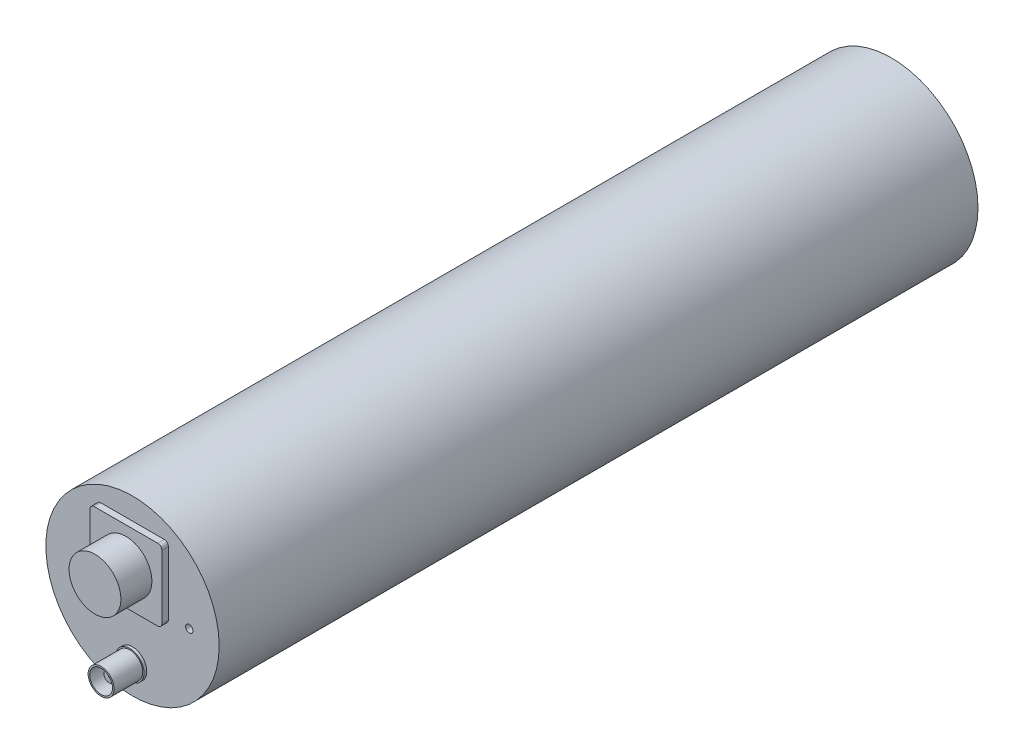
SolidWorks part; units mm, degrees
ref_plane "Front Plane" through (0, 0, 0) normal (0, 0, 1) x (1, 0, 0)
ref_plane "Top Plane" through (0, 0, 0) normal (0, 1, 0) x (1, 0, 0)
ref_plane "Right Plane" through (0, 0, 0) normal (1, 0, 0) x (0, 0, -1)
ref_axis "Axis1" through (0, 0, -88.99) along (0, 0, 1)
ref_axis "Axis2" through (0, -55, 0) along (0, 1, 0)
ref_axis "Axis3" through (-88.99, 0, 0) along (1, 0, 0)
sketch "Sketch1" plane through (0, 0, 0) normal (0, 0, 1) x (1, 0, 0)
  circle A0 centre (0, 0) radius 31.75
  dimension "D1" = 63.5
extrude "Boss-Extrude1" add sketch "Sketch1" along normal mid plane 278
sketch "Sketch3" plane through (0, 0, 139) normal (0, 0, 1) x (1, 0, 0)
  line L0 (-20.7962, 0) -> (20.7962, 0) construction
  line L1 (11.6445, -2.539) -> (-11.6445, -2.539)
  line L2 (13.1445, -1.039) -> (13.1445, 22.25)
  line L3 (11.6445, 23.75) -> (-11.6445, 23.75)
  line L4 (-13.1445, -1.039) -> (-13.1445, 22.25)
  line L5 (13.1445, -2.539) -> (-13.1445, 23.75) construction
  line L6 (13.1445, 23.75) -> (-13.1445, -2.539) construction
  line L7 (0, 0) -> (0, -21.35) construction
  arc A0 (13.1445, 22.25) -> (11.6445, 23.75) centre (11.6445, 22.25) ccw
  circle A2 centre (0, 0) radius 31.75 construction
  circle A3 centre (0, 10.6055) radius 9.5
  arc A4 (11.6445, -2.539) -> (13.1445, -1.039) centre (11.6445, -1.039) ccw
  arc A5 (-11.6445, -2.539) -> (-13.1445, -1.039) centre (-11.6445, -1.039) cw
  arc A6 (-11.6445, 23.75) -> (-13.1445, 22.25) centre (-11.6445, 22.25) ccw
  point P0 (0, 10.6055)
  point P10 (0, 0)
  dimension "D2" = 26.289
  dimension "D5" = 19
  dimension "D6" = 1.5
  dimension "D1" = 41.5925
  dimension "D3" = 8
  dimension "D4" = 10.4
extrude "Boss-Extrude2" add sketch "Sketch3" along normal blind 2.4
extrude "Boss-Extrude3" add sketch "Sketch3<2>" along normal blind 13.75 contours A3 region at (0, 10.6055, 139)
sketch "Sketch3<2>" plane through (0, 0, 139) normal (0, 0, 1) x (1, 0, 0) same geometry as "Sketch3"
ref_plane "Plane1" through (0, -21.35, 0) normal (0, 1, 0) x (1, 0, 0)
sketch "Sketch4" plane through (0, -21.35, 0) normal (0, 1, 0) x (1, 0, 0)
  line L0 (0, -139) -> (0, -143.5)
  line L1 (0, -143.5) -> (-0.25, -143.5)
  line L2 (-0.25, -143.5) -> (-0.25, -147.5)
  line L3 (-0.25, -147.5) -> (-2, -147.5)
  line L4 (-2, -147.5) -> (-2, -141)
  line L5 (-2, -141) -> (-4.175, -141)
  line L6 (-4.175, -141) -> (-4.175, -150.5)
  line L7 (-4.175, -150.5) -> (-4.75, -150.5)
  line L8 (-4.75, -150.5) -> (-4.75, -140)
  line L10 (-5.22, -139) -> (0, -139)
  line L11 (0, -143.5) -> (0, -147.5) construction
  line L12 (-4.75, -140) -> (-5.22, -140)
  line L13 (-5.22, -140) -> (-5.22, -139)
  line L14 (13.1445, -139) -> (-13.1445, -139) construction
  dimension "D1" = 9.5
  dimension "D2" = 10.44
  dimension "D3" = 8.35
  dimension "D4" = 2
  dimension "D5" = 0.5
  dimension "D6" = 11.5
  dimension "D7" = 3
  dimension "D8" = 4
  dimension "D9" = 2
  dimension "D10" = 1
revolve "Revolve1" add sketch "Sketch4" angle 360 about L11
hole_wizard "#6-32 Tapped Hole1" positions "Sketch6" profile "Sketch5" tap size "#6-32" standard "ANSI Inch"
sketch "Sketch6" plane through (0, 0, 139) normal (0, 0, 1) x (1, 0, 0)
  point P0 (-20.7962, 0)
  point P2 (20.7962, 0)
sketch "Sketch5" plane through (-20.7962, 0, 139) normal (1, 0, 0) x (0, -1, 0)
  line L0 (0, 0) -> (0, 10.2027)
  line L1 (0, 10.2027) -> (1.3525, 9.39)
  line L2 (1.3525, 9.39) -> (1.3525, 0)
  line L5 (1.3525, 0) -> (0, 0)
  line L10 (0, 10.2027) -> (-1.3525, 9.39) construction
  line L11 (0, -6.35) -> (0, 107.95) construction
  dimension "Tap Drill Dia." = 2.7051
  dimension "Tap Drill Depth" = 9.39
  dimension "Drill Angle" = 118
sketch "Sketch7" plane through (0, 0, -139) normal (0, 0, -1) x (-1, 0, 0)
  line L0 (0, 0) -> (20.75, 0) construction
  line L1 (14.9521, -2.3338) -> (18.4162, -5.7979)
  line L2 (16.1312, 8) -> (11.5124, 0)
  line L3 (11.5124, 0) -> (16.1312, -8)
  line L4 (16.1312, -8) -> (25.3688, -8)
  line L5 (25.3688, -8) -> (29.9876, 0)
  line L6 (29.9876, 0) -> (25.3688, 8)
  line L7 (25.3688, 8) -> (16.1312, 8)
  line L8 (16.6841, -4.0659) -> (20.75, 0) construction
  circle A0 centre (20.75, 0) radius 8 construction
  circle A1 centre (20.75, 0) radius 6.25
  circle A2 centre (20.75, 0) radius 5
  circle A4 centre (0, 0) radius 31.75 construction
  dimension "D3" = 12.5
  dimension "D4" = 10
  dimension "D1" = 45
  dimension "D2" = 16
  dimension "D5" = 5.75
  dimension "D6" = 11
extrude "Boss-Extrude4" add sketch "Sketch7" along normal blind 2.5 contours L6 L7 L2 L3 L4 L5 A1 region at (-20.75, 7.7556, -139)
extrude "Boss-Extrude5" add sketch "Sketch7<3>" along normal blind 8.33 contours L1 A1 A2 region at (-19.595, 5.9624, -139)
sketch "Sketch7<3>" plane through (0, 0, -139) normal (0, 0, -1) x (-1, 0, 0) same geometry as "Sketch7"
extrude "Boss-Extrude6" add sketch "Sketch7<4>" along normal blind 18.5 contours A2 region at (-20.75, 0, -139)
sketch "Sketch7<4>" plane through (0, 0, -139) normal (0, 0, -1) x (-1, 0, 0) same geometry as "Sketch7"
sketch "Sketch8" plane through (0, 0, -139) normal (0, 0, -1) x (-1, 0, 0)
  line L1 (7.9125, 25.2) -> (-15.9125, 25.2)
  line L2 (9.5, 23.6125) -> (9.5, -23.6125)
  line L3 (7.9125, -25.2) -> (-15.9125, -25.2)
  line L4 (-17.5, 23.6125) -> (-17.5, -23.6125)
  line L5 (9.5, 25.2) -> (-17.5, -25.2) construction
  line L6 (9.5, -25.2) -> (-17.5, 25.2) construction
  arc A0 (-15.9125, -25.2) -> (-17.5, -23.6125) centre (-15.9125, -23.6125) cw
  arc A1 (9.5, -23.6125) -> (7.9125, -25.2) centre (7.9125, -23.6125) cw
  arc A2 (7.9125, 25.2) -> (9.5, 23.6125) centre (7.9125, 23.6125) cw
  arc A3 (-15.9125, 25.2) -> (-17.5, 23.6125) centre (-15.9125, 23.6125) ccw
  point P0 (-4, 0)
  dimension "D3" = 1.5875
  dimension "D1" = 27
  dimension "D2" = 50.4
  dimension "D4" = 4
extrude "Boss-Extrude7" add sketch "Sketch8" along normal blind 0.5
